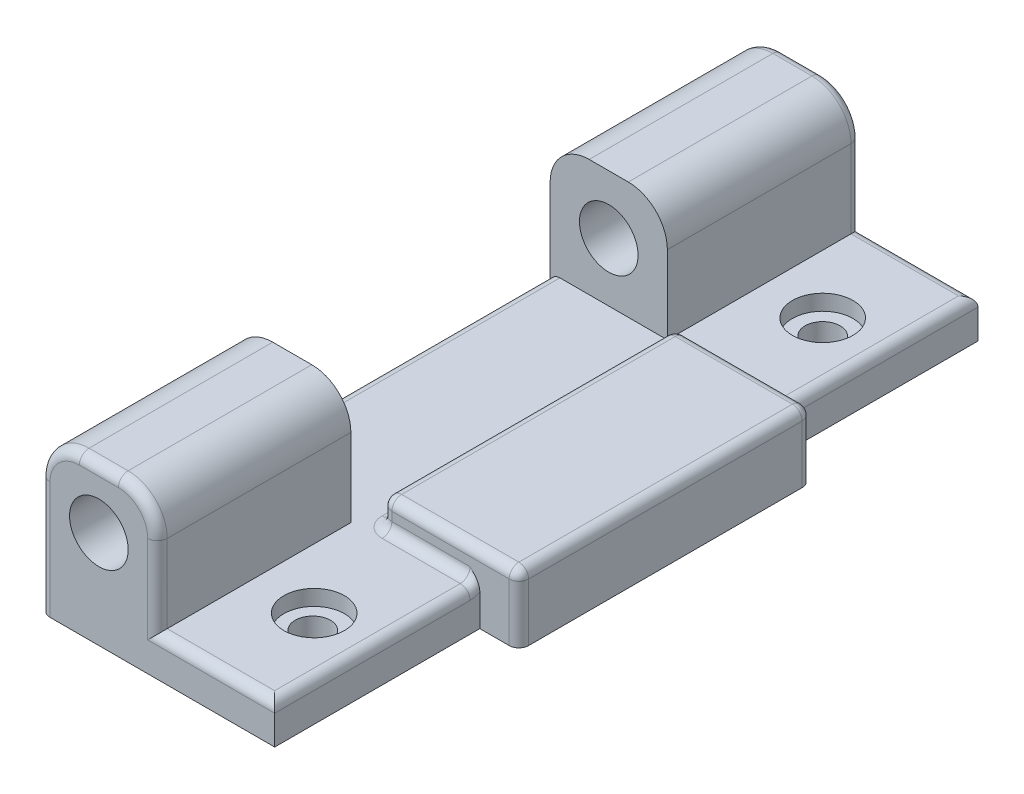
SolidWorks part; units mm, degrees
material "PA Type 6"
ref_plane "Front Plane" through (0, 0, 0) normal (0, 0, 1) x (1, 0, 0)
ref_plane "Top Plane" through (0, 0, 0) normal (0, 1, 0) x (1, 0, 0)
ref_plane "Right Plane" through (0, 0, 0) normal (1, 0, 0) x (0, 0, -1)
sketch "Sketch2" plane through (0, 0, 0) normal (0, 1, 0) x (1, 0, 0)
  line L0 (-54.3874, 9.3729) -> (-42.3874, 9.3729) construction
  line L1 (-54.3874, 27.3729) -> (-42.3874, 27.3729)
  line L2 (-54.3874, 27.3729) -> (-54.3874, -8.6271)
  line L3 (-54.3874, -8.6271) -> (-42.3874, -8.6271)
  line L4 (-42.3874, 27.3729) -> (-42.3874, -8.6271)
  dimension "D1" = 18
  dimension "D2" = 12
extrude "Boss-Extrude1" add sketch "Sketch2" along normal blind 2 contours L2 L3 L4 L1
sketch "Sketch3" plane through (0, 2, 0) normal (0, 1, 0) x (1, 0, 0)
  line L1 (-54.3874, -8.6271) -> (-48.3874, -8.6271)
  line L2 (-54.3874, -8.6271) -> (-54.3874, 1.2729)
  line L3 (-54.3874, 1.2729) -> (-48.3874, 1.2729)
  line L4 (-48.3874, -8.6271) -> (-48.3874, 1.2729)
  line L5 (-54.3874, 27.3729) -> (-48.3874, 27.3729)
  line L6 (-54.3874, 27.3729) -> (-54.3874, 17.4729)
  line L7 (-54.3874, 17.4729) -> (-48.3874, 17.4729)
  line L8 (-48.3874, 27.3729) -> (-48.3874, 17.4729)
  dimension "D1" = 9.9
  dimension "D2" = 6
  dimension "D3" = 9.9
  dimension "D4" = 6
extrude "Boss-Extrude2" add sketch "Sketch3" along normal blind 6
sketch "Sketch4" plane through (0, 0, -27.3729) normal (0, 0, -1) x (-1, 0, 0)
  line L0 (51.3874, 8) -> (51.3874, 0)
  line L1 (48.3874, 8) -> (54.3874, 8) construction
  line L2 (54.3874, 0) -> (42.3874, 0) construction
  line L3 (48.3874, 5) -> (54.3874, 5) construction
  line L4 (48.3874, 8) -> (48.3874, 2) construction
  line L5 (54.3874, 8) -> (54.3874, 0) construction
  point P12 (51.3874, 5)
  dimension "D1" = 3
hole_wizard "Ø3.0mm Dowel Hole1" positions "Sketch5" profile "Sketch6" hole size "Ø3.0" standard "ISO" end condition through all
sketch "Sketch5" plane through (0, 0, -27.3729) normal (0, 0, -1) x (-1, 0, 0)
  point P0 (51.3874, 5)
sketch "Sketch6" plane through (-51.3874, 5, -27.3729) normal (1, 0, 0) x (0, 1, 0)
  line L0 (0, 0) -> (0, 36)
  line L1 (0, 36) -> (1.5, 36)
  line L2 (1.5, 36) -> (1.5, 0)
  line L5 (1.5, 0) -> (0, 0)
  line L11 (0, -6.35) -> (0, 107.95) construction
  dimension "Thru Hole Dia." = 3
  dimension "Thru Hole Depth" = 36
fillet "Fillet1" radius 2 4 edges at (-54.3874, 8, -22.4229) (-48.3874, 8, -22.4229) (-54.3874, 8, 3.6771) (-48.3874, 8, 3.6771)
sketch "Sketch7" plane through (0, 2, 0) normal (0, 1, 0) x (1, 0, 0)
  line L0 (-48.3874, -3.6771) -> (-42.3874, -3.6771) construction
  line L1 (-48.3874, -8.6271) -> (-48.3874, 1.2729) construction
  line L2 (-42.3874, 27.3729) -> (-42.3874, -8.6271) construction
  line L3 (-48.3874, 22.4229) -> (-42.3874, 22.4229) construction
  line L4 (-48.3874, 17.4729) -> (-48.3874, 27.3729) construction
  line L5 (-45.3874, -8.6271) -> (-45.3874, 27.3729) construction
  line L6 (-48.3874, -8.6271) -> (-42.3874, -8.6271) construction
  line L7 (-48.3874, 27.3729) -> (-42.3874, 27.3729) construction
  circle A4 centre (-45.3874, -3.6771) radius 0.9
  circle A5 centre (-45.3874, 22.4229) radius 0.9
  point P16 (-45.3874, -3.6771)
  point P17 (-45.3874, 22.4229)
  dimension "D1" = 1.8
sketch "Sketch10" plane through (-42.3874, 0, 0) normal (1, 0, 0) x (0, 0, -1)
  line L0 (27.3729, 2) -> (-8.6271, 2) construction
  line L1 (1.8729, 2) -> (16.8729, 2)
  line L2 (1.8729, 2) -> (1.8729, 0)
  line L3 (1.8729, 0) -> (16.8729, 0)
  line L4 (16.8729, 2) -> (16.8729, 0)
  line L5 (27.3729, 0) -> (-8.6271, 0) construction
  line L6 (-8.6271, 2) -> (-8.6271, 0) construction
  line L7 (27.3729, 2) -> (27.3729, 0) construction
  dimension "D1" = 10.5
  dimension "D2" = 10.5
extrude "Boss-Extrude3" add sketch "Sketch10" along normal blind 2
sketch "Sketch11" plane through (0, 2, 0) normal (0, 1, 0) x (1, 0, 0)
  line L0 (-40.3874, 1.8729) -> (-47.3874, 1.8729)
  line L2 (-40.3874, 1.8729) -> (-40.3874, 16.8729)
  line L3 (-47.3874, 1.8729) -> (-47.3874, 16.8729)
  line L4 (-47.3874, 16.8729) -> (-40.3874, 16.8729)
  line L6 (-40.3874, 16.8729) -> (-40.3874, 1.8729) construction
  line L7 (-40.3874, 16.8729) -> (-42.3874, 16.8729) construction
  dimension "D1" = 7
extrude "Boss-Extrude4" add sketch "Sketch11" along normal blind 1.45
fillet "Fillet2" radius 0.5 4 edges at (-40.3874, 1.725, -16.8729) (-40.3874, 1.725, -1.8729) (-43.8874, 3.45, -16.8729) (-43.8874, 3.45, -1.8729)
sketch "Sketch12" plane through (0, 3.45, 0) normal (0, 1, 0) x (1, 0, 0)
  line L0 (-57.8552, 9.3729) -> (-37.4911, 9.3729) construction
sketch "Sketch13" plane through (0, 0, 0) normal (0, -1, 0) x (1, 0, 0)
  line L0 (-54.3874, -9.3729) -> (-33.3474, -9.3729) construction
  line L1 (-54.3874, -27.3729) -> (-54.3874, 8.6271) construction
  dimension "D1" = 21.04
fillet "Fillet5" radius 0.5 3 edges at (-40.3874, 3.45, -9.3729) (-40.5338, 3.3036, -2.0194) (-40.5338, 3.3036, -16.7265)
fillet "Fillet6" radius 0.5 8 edges at (-44.8874, 2, -16.8729) (-44.8874, 2, -1.8729) (-47.3874, 2.475, -16.8729) (-47.3874, 3.3036, -16.7265) (-47.3874, 2.475, -1.8729) (-47.3874, 3.3036, -2.0194) (-47.3874, 3.45, -9.3729) (-47.3874, 2, -9.3729)
extrude "Cut-Extrude5" cut sketch "Sketch7" against normal through all
sketch "Sketch19" plane through (0, 2, 0) normal (0, 1, 0) x (1, 0, 0)
  line L0 (-46.2874, -3.6771) -> (-44.4874, -3.6771) construction
  line L1 (-45.3874, -4.5771) -> (-45.3874, -2.7771) construction
  line L2 (-46.2874, 22.4229) -> (-44.4874, 22.4229) construction
  line L3 (-45.3874, 21.5229) -> (-45.3874, 23.3229) construction
  circle A0 centre (-45.3874, -3.6771) radius 0.9 construction
  circle A1 centre (-45.3874, 22.4229) radius 0.9 construction
  circle A2 centre (-45.3163, -3.6771) radius 1.55
  circle A3 centre (-45.3874, 22.4229) radius 1.55
  dimension "D1" = 3.1
extrude "Cut-Extrude6" cut sketch "Sketch19" against normal blind 0.8
fillet "Fillet7" radius 0.5 17 edges at (-54.3874, 3, 8.6271) (-53.8016, 7.4142, 8.6271) (-51.3874, 8, 8.6271) (-48.9731, 7.4142, 8.6271) (-54.3874, 3, -27.3729) (-53.8016, 7.4142, -27.3729) (-51.3874, 8, -27.3729) (-48.9731, 7.4142, -27.3729) (-42.3874, 2.1464, -17.0194) (-42.3874, 2.1464, -1.7265) (-48.3874, 4, 8.6271) (-48.3874, 4, -27.3729) (-45.3874, 2, -27.3729) (-42.3874, 2, -22.3729) (-42.3874, 2, 3.6271) (-45.3874, 2, 8.6271) (-54.3874, 2, -9.3729)
